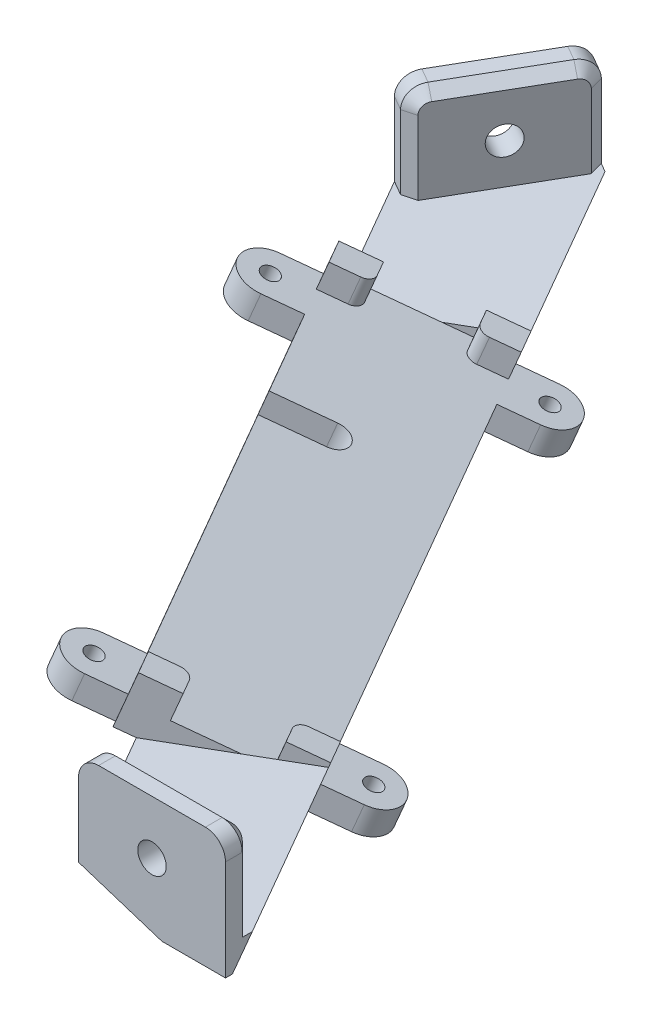
SolidWorks part; units mm, degrees
ref_plane "Front Plane" through (0, 0, 0) normal (0, 0, 1) x (1, 0, 0)
ref_plane "Top Plane" through (0, 0, 0) normal (0, 1, 0) x (1, 0, 0)
ref_plane "Right Plane" through (0, 0, 0) normal (1, 0, 0) x (0, 0, -1)
sketch "Sketch1" plane through (0, 0, 0) normal (0, 1, 0) x (1, 0, 0)
  line L9 (0, 0) -> (48, 0) construction
  line L10 (48, 0) -> (404, 0) construction
  line L11 (404, 0) -> (452, 0) construction
  line L12 (452, 0) -> (428, 41.5692) construction
  line L13 (428, 41.5692) -> (250, 349.8743) construction
  line L14 (250, 349.8743) -> (226, 391.4435) construction
  line L15 (226, 391.4435) -> (202, 349.8743) construction
  line L16 (202, 349.8743) -> (24, 41.5692) construction
  line L17 (24, 41.5692) -> (0, 0) construction
  line L18 (48, 0) -> (24, 41.5692) construction
  line L19 (202, 349.8743) -> (250, 349.8743) construction
  line L20 (428, 41.5692) -> (404, 0) construction
  line L22 (15.3397, 46.5692) -> (193.3397, 354.8743) construction
  line L28 (404, -10) -> (48, -10) construction
  line L30 (48, -10) -> (48, 10) construction
  line L31 (404, -10) -> (404, 10) construction
  line L32 (15.3397, 46.5692) -> (32.6603, 36.5692) construction
  line L33 (193.3397, 354.8743) -> (210.6603, 344.8743) construction
  line L34 (404, 10) -> (48, 10) construction
  line L35 (32.6603, 36.5692) -> (210.6603, 344.8743) construction
  line L40 (81.735, 121.5692) -> (146.1495, 10)
  line L45 (81.735, 121.5692) -> (93.8594, 142.5692)
  line L46 (93.8594, 142.5692) -> (170.3983, 10)
  line L47 (170.3983, 10) -> (146.1495, 10)
  dimension "D1" = 356
  dimension "D2" = 48
  dimension "D3" = 10
  dimension "D4" = 90
  dimension "D5" = 21
extrude "Boss-Extrude1" add sketch "Sketch1" along normal blind 4
sketch "Sketch2" plane through (0, 4, 0) normal (0, 1, 0) x (1, 0, 0)
  line L0 (93.8594, 142.5692) -> (81.735, 121.5692)
  line L1 (81.735, 121.5692) -> (84.0444, 117.5692)
  line L2 (81.735, 121.5692) -> (146.1495, 10) construction
  line L3 (84.0444, 117.5692) -> (96.1688, 138.5692)
  line L4 (170.3983, 10) -> (93.8594, 142.5692) construction
  line L5 (96.1688, 138.5692) -> (93.8594, 142.5692)
  line L6 (146.1495, 10) -> (170.3983, 10)
  line L7 (170.3983, 10) -> (168.0889, 14)
  line L8 (168.0889, 14) -> (143.8401, 14)
  line L9 (143.8401, 14) -> (146.1495, 10)
  dimension "D1" = 4
  dimension "D2" = 4
extrude "Boss-Extrude2" add sketch "Sketch2" along normal blind 14
sketch "Sketch5" plane through (0, 4, 0) normal (0, 1, 0) x (1, 0, 0)
  line L0 (96.1688, 138.5692) -> (92.7047, 140.5692)
  line L1 (93.8594, 142.5692) -> (81.735, 121.5692) construction
  line L2 (92.7047, 140.5692) -> (93.8594, 142.5692)
  line L3 (93.8594, 142.5692) -> (96.1688, 138.5692)
  line L4 (81.735, 121.5692) -> (85.1991, 119.5692)
  line L5 (84.0444, 117.5692) -> (96.1688, 138.5692) construction
  line L6 (85.1991, 119.5692) -> (84.0444, 117.5692)
  line L7 (84.0444, 117.5692) -> (81.735, 121.5692)
  line L8 (146.1495, 10) -> (146.1495, 14)
  line L9 (168.0889, 14) -> (143.8401, 14) construction
  line L10 (146.1495, 14) -> (143.8401, 14)
  line L11 (143.8401, 14) -> (146.1495, 10)
  line L12 (168.0889, 14) -> (168.0889, 10)
  line L13 (146.1495, 10) -> (170.3983, 10) construction
  line L14 (168.0889, 10) -> (170.3983, 10)
  line L15 (170.3983, 10) -> (168.0889, 14)
extrude "Cut-Extrude3" cut sketch "Sketch5" along normal through all
sketch "Sketch6" plane through (0, 4, 0) normal (0, 1, 0) x (1, 0, 0)
  line L0 (93.8594, 142.5692) -> (96.1688, 138.5692)
  line L1 (96.1688, 138.5692) -> (92.7047, 140.5692)
  line L2 (92.7047, 140.5692) -> (93.8594, 142.5692)
  line L3 (168.0889, 14) -> (168.0889, 10)
  line L4 (168.0889, 10) -> (170.3983, 10)
  line L5 (170.3983, 10) -> (168.0889, 14)
extrude "Cut-Extrude4" cut sketch "Sketch6" against normal through all
sketch "Sketch7" plane through (0, 0, -10) normal (0, 0, 1) x (1, 0, 0)
  line L0 (157.1192, 18) -> (157.1192, 0) construction
  line L1 (146.1495, 18) -> (168.0889, 18) construction
  line L2 (146.1495, 0) -> (168.0889, 0) construction
  circle A0 centre (157.1192, 10) radius 2.125
  dimension "D1" = 4.25
  dimension "D2" = 10
extrude "Cut-Extrude5" cut sketch "Sketch7" against normal up to surface (4 mm away) up to face at (157.1192, 11, -14)
sketch "Sketch8" plane through (8.6603, 0, 5) normal (-0.866, 0, -0.5) x (-0.5, 0, 0.866)
  line L0 (-157.1192, 18) -> (-157.1192, 0) construction
  line L1 (-168.0889, 18) -> (-146.1495, 18) construction
  line L2 (-168.0889, 0) -> (-146.1495, 0) construction
  circle A0 centre (-157.1192, 10) radius 2.125
  dimension "D1" = 4.25
  dimension "D2" = 10
extrude "Cut-Extrude6" cut sketch "Sketch8" against normal up to surface (4 mm away) up to face at (90.684, 11, -129.0692)
fillet "Fillet1" radius 3 4 edges at (94.4367, 18, -139.5692) (83.4671, 18, -120.5692) (146.1495, 18, -12) (168.0889, 18, -12)
chamfer "Chamfer1" distance 1.5 angle 45 10 edges at (146.1495, 9.5, -14) (147.0282, 17.1213, -14) (157.1192, 18, -14) (167.2102, 17.1213, -14) (168.0889, 9.5, -14) (96.1688, 9.5, -138.5692) (95.7294, 17.1213, -137.8083) (90.684, 18, -129.0692) (85.6385, 17.1213, -120.3302) (85.1991, 9.5, -119.5692)
ref_plane "Plane1" through (0, 0, 0) normal (0.5, 0, 0.866) x (0.866, 0, -0.5)
sketch "Sketch10" plane through (0, 0, 0) normal (0.5, 0, 0.866) x (0.866, 0, -0.5)
  line L0 (152.5692, 4) -> (131.5692, 4)
  line L5 (152.5692, 4) -> (131.5692, 11.7949)
  line L6 (131.5692, 15) -> (131.5692, 4) construction
  line L7 (131.5692, 11.7949) -> (131.5692, 4) construction
  line L8 (131.5692, 11.7949) -> (129.0263, 4.9439)
  line L9 (129.0263, 4.9439) -> (131.5692, 4)
  dimension "D1" = 22.4
extrude "Boss-Extrude3" add sketch "Sketch10" along normal blind 40.85 and the other way blind 40.85
sketch "Sketch11" plane through (0, 0, 0) normal (0.5, 0, 0.866) x (0.866, 0, -0.5)
  line L0 (152.5692, 4) -> (151.0845, 0)
  line L1 (151.0845, 0) -> (152.5692, 0)
  line L2 (152.5692, 0) -> (152.5692, 4)
  line L3 (152.5692, 0) -> (152.5692, 4) construction
  line L4 (131.5692, 11.7949) -> (129.0263, 4.9439) construction
  line L7 (152.5692, 0) -> (150.5692, 0) construction
extrude "Cut-Extrude7" cut sketch "Sketch11" against normal through all both and the other way through all
sketch "Sketch12" plane through (17.1301, 53.2892, -9.8901) normal (0.3014, 0.9375, -0.174) x (0.9535, -0.2963, 0.055)
  line L0 (80.1117, 97.311) -> (99.1849, 109.0571)
  line L1 (99.1849, 109.0571) -> (142.0267, 39.4907)
  line L2 (142.0267, 39.4907) -> (122.9534, 27.7447)
  line L3 (122.9534, 27.7447) -> (80.1117, 97.311)
extrude "Cut-Extrude8" cut sketch "Sketch12" against normal blind 3.3077
sketch "Sketch14" plane through (16.1333, 50.1883, -9.3145) normal (0.3014, 0.9375, -0.174) x (0.9535, -0.2963, 0.055)
  line L0 (80.1117, 97.311) -> (84.5394, 100.0378)
  line L1 (91.5972, 104.3842) -> (80.1117, 97.311) construction
  line L2 (84.5394, 100.0378) -> (85.8503, 97.909)
  line L3 (85.3597, 95.8453) -> (82.2092, 93.905)
  line L4 (80.1117, 97.311) -> (122.9534, 27.7447) construction
  line L5 (82.2092, 93.905) -> (80.1117, 97.311)
  line L6 (99.1849, 109.0571) -> (94.7572, 106.3303)
  line L7 (99.1849, 109.0571) -> (91.5972, 104.3842) construction
  line L8 (94.7572, 106.3303) -> (96.0681, 104.2016)
  line L9 (98.1319, 103.7109) -> (101.2824, 105.6511)
  line L10 (142.0267, 39.4907) -> (99.1849, 109.0571) construction
  line L11 (101.2824, 105.6511) -> (99.1849, 109.0571)
  line L12 (122.9534, 27.7447) -> (120.8559, 31.1506)
  line L13 (80.1117, 97.311) -> (122.9534, 27.7447) construction
  line L14 (120.8559, 31.1506) -> (124.0064, 33.0908)
  line L15 (126.0702, 32.6001) -> (127.3811, 30.4714)
  line L16 (122.9534, 27.7447) -> (134.4389, 34.8179) construction
  line L17 (127.3811, 30.4714) -> (122.9534, 27.7447)
  line L18 (142.0267, 39.4907) -> (137.5989, 36.764)
  line L19 (142.0267, 39.4907) -> (134.4389, 34.8179) construction
  line L20 (137.5989, 36.764) -> (136.288, 38.8927)
  line L21 (136.7787, 40.9565) -> (139.9292, 42.8967)
  line L22 (139.9292, 42.8967) -> (142.0267, 39.4907)
  arc A0 (136.288, 38.8927) -> (136.7787, 40.9565) centre (137.5652, 39.6793) cw
  arc A1 (98.1319, 103.7109) -> (96.0681, 104.2016) centre (97.3454, 104.9882) cw
  arc A2 (85.8503, 97.909) -> (85.3597, 95.8453) centre (84.5731, 97.1225) cw
  arc A3 (124.0064, 33.0908) -> (126.0702, 32.6001) centre (124.793, 31.8136) cw
  point P36 (135.5014, 40.1699)
  dimension "D3" = 1.5
  dimension "D1" = 4
  dimension "D2" = 5.2
extrude "Boss-Extrude4" add sketch "Sketch14" along normal blind 4
sketch "Sketch15" plane through (20.425, 0, 35.3771) normal (0.5, 0, 0.866) x (0.866, 0, -0.5)
  line L0 (129.0263, 4.9439) -> (150.0263, -2.851)
  line L1 (150.0263, -2.851) -> (151.0845, 0)
  line L2 (152.5692, 4) -> (151.0845, 0) construction
  line L3 (129.0263, 4.9439) -> (131.5692, 4) construction
  line L4 (151.0845, 0) -> (129.0263, 4.9439)
extrude "Boss-Extrude5" add sketch "Sketch15" against normal up to surface (81.7 mm away) up to face at (96.1201, 7.1511, -102.6645)
sketch "Sketch13" plane through (16.1333, 50.1883, -9.3145) normal (0.3014, 0.9375, -0.174) x (0.9535, -0.2963, 0.055)
  line L0 (86.9235, 101.506) -> (100.2952, 79.7931) construction
  line L1 (82.4213, 98.7334) -> (91.5972, 104.3842) construction
  line L2 (82.2092, 93.905) -> (120.8559, 31.1506) construction
  line L3 (94.6632, 73.6823) -> (101.475, 77.8773)
  line L4 (94.6632, 73.6823) -> (92.3035, 77.514)
  line L5 (92.3035, 77.514) -> (99.1153, 81.709)
  line L6 (91.5972, 104.3842) -> (84.5394, 100.0378) construction
  circle A0 centre (100.2952, 79.7931) radius 2.25 construction
  arc A1 (99.1153, 81.709) -> (101.475, 77.8773) centre (100.2952, 79.7931) cw
  dimension "D2" = 4.5
  dimension "D1" = 25.5
  dimension "D3" = 8
extrude "Cut-Extrude9" cut sketch "Sketch13" against normal through all
sketch "Sketch16" plane through (16.1333, 50.1883, -9.3145) normal (0.3014, 0.9375, -0.174) x (0.9535, -0.2963, 0.055)
  line L0 (99.7355, 108.163) -> (80.6623, 96.4169) construction
  line L1 (139.9292, 42.8967) -> (101.2824, 105.6511) construction
  line L2 (82.2092, 93.905) -> (92.3035, 77.514) construction
  line L3 (82.4213, 98.7334) -> (91.5972, 104.3842) construction
  line L4 (78.3385, 90.4644) -> (106.097, 107.5591) construction
  line L5 (120.6058, 74.2739) -> (101.5325, 62.5278) construction
  line L6 (94.6632, 73.6823) -> (120.8559, 31.1506) construction
  line L7 (99.7355, 108.163) -> (104.0781, 110.8373)
  line L8 (103.7732, 101.6066) -> (108.1158, 104.2809)
  line L9 (99.7355, 108.163) -> (103.7732, 101.6066)
  line L10 (76.3197, 93.7426) -> (80.6623, 96.4169)
  line L11 (80.3574, 87.1862) -> (84.7, 89.8605)
  line L12 (84.7, 89.8605) -> (80.6623, 96.4169)
  line L13 (141.4761, 40.3848) -> (145.8186, 43.0591)
  line L14 (137.4384, 46.9412) -> (141.7809, 49.6156)
  line L15 (141.4761, 40.3848) -> (137.4384, 46.9412)
  line L16 (118.3651, 35.1952) -> (122.4028, 28.6387)
  line L17 (118.0602, 25.9644) -> (122.4028, 28.6387)
  line L18 (114.0225, 32.5208) -> (118.3651, 35.1952)
  circle A0 centre (106.097, 107.5591) radius 2.85 construction
  circle A1 centre (78.3385, 90.4644) radius 2.85 construction
  circle A2 centre (106.097, 107.5591) radius 3.85 construction
  circle A3 centre (78.3385, 90.4644) radius 3.85 construction
  arc A4 (104.0781, 110.8373) -> (108.1158, 104.2809) centre (106.097, 107.5591) cw
  arc A5 (76.3197, 93.7426) -> (80.3574, 87.1862) centre (78.3385, 90.4644) ccw
  arc A6 (145.8186, 43.0591) -> (141.7809, 49.6156) centre (143.7998, 46.3374) ccw
  arc A7 (118.0602, 25.9644) -> (114.0225, 32.5208) centre (116.0414, 29.2426) cw
  circle A8 centre (78.3385, 90.4644) radius 1.25
  circle A9 centre (106.097, 107.5591) radius 1.25
  circle A10 centre (143.7998, 46.3374) radius 1.25
  circle A11 centre (116.0414, 29.2426) radius 1.25
  dimension "D2" = 5.7
  dimension "D7" = 2.5
  dimension "D1" = 1.05
  dimension "D5" = 5.1
  dimension "D6" = 5.1
  dimension "D3" = 1
  dimension "D4" = 1
extrude "Boss-Extrude6" add sketch "Sketch16" against normal blind 4
sketch "Sketch18" plane through (20.425, 0, 35.3771) normal (0.5, 0, 0.866) x (0.866, 0, -0.5)
  line L0 (131.5692, 4) -> (142.3455, 0)
  line L1 (142.3455, 0) -> (131.5692, 0)
  line L2 (131.5692, 0) -> (131.5692, 4)
extrude "Cut-Extrude10" cut sketch "Sketch18" against normal through all both and the other way through all
